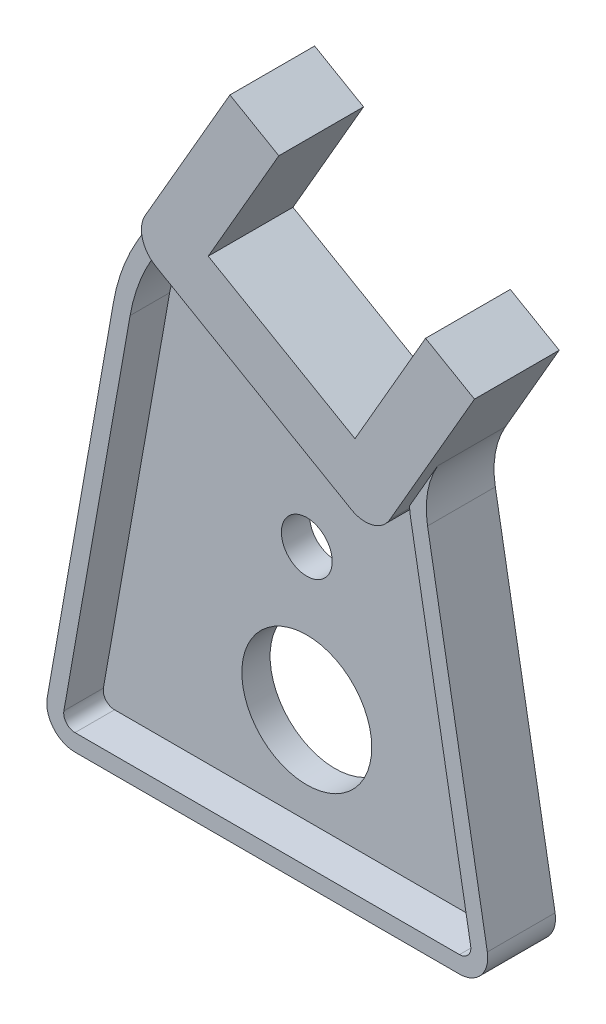
SolidWorks part; units mm, degrees
ref_plane "Front Plane" through (0, 0, 0) normal (0, 0, 1) x (1, 0, 0)
ref_plane "Top Plane" through (0, 0, 0) normal (0, 1, 0) x (1, 0, 0)
ref_plane "Right Plane" through (0, 0, 0) normal (1, 0, 0) x (0, 0, -1)
sketch "Sketch1" plane through (0, 0, 0) normal (0, 0, 1) x (1, 0, 0)
  line L0 (-34.0412, 0) -> (34.0412, 0)
  line L1 (0, 0) -> (0, 75) construction
  line L2 (-38.9653, 5.8682) -> (-27.243, 72.3487)
  line L3 (-18.6122, 91.5192) -> (-3.6122, 117.5)
  line L4 (-3.6122, 117.5) -> (5.0481, 112.5)
  line L5 (5.0481, 112.5) -> (-7.4519, 90.8494)
  line L6 (-7.4519, 90.8494) -> (18.5289, 75.8494)
  line L7 (18.5289, 75.8494) -> (31.0289, 97.5)
  line L8 (31.0289, 97.5) -> (39.6891, 92.5)
  line L9 (39.6891, 92.5) -> (30.1627, 75.9997)
  line L10 (17.859, 64.6891) -> (-16.782, 84.6891)
  line L11 (28.3809, 65.895) -> (38.9653, 5.8682)
  line L12 (5.5385, 83.3494) -> (18.0385, 105) construction
  line L13 (5.5385, 83.3494) -> (0, 75) construction
  line L14 (5.0481, 112.5) -> (31.0289, 97.5) construction
  line L15 (24.6891, 66.5192) -> (30.1627, 75.9997)
  line L16 (-23.0856, 83.771) -> (-18.6122, 91.5192)
  line L17 (25.4265, 65.3741) -> (36.0108, 5.3473)
  line L18 (-34.0412, 3) -> (34.0412, 3)
  line L19 (-36.0108, 5.3473) -> (-24.2885, 71.8278)
  line L20 (-20.4875, 82.271) -> (-18.3054, 86.0506)
  line L21 (-20.4875, 82.271) -> (-16.0141, 90.0192) construction
  circle A0 centre (0, 20) radius 11.5
  circle A1 centre (0, 45) radius 4.5
  arc A2 (34.0412, 0) -> (38.9653, 5.8682) centre (34.0412, 5) ccw
  arc A3 (-34.0412, 0) -> (-38.9653, 5.8682) centre (-34.0412, 5) cw
  arc A4 (-27.243, 72.3487) -> (-23.0856, 83.771) centre (7.2253, 66.271) cw
  arc A5 (28.3809, 65.895) -> (30.1627, 75.9997) centre (43.1531, 68.4997) cw
  arc A6 (24.6891, 66.5192) -> (17.859, 64.6891) centre (20.359, 69.0192) cw
  arc A7 (-16.782, 84.6891) -> (-18.6122, 91.5192) centre (-14.282, 89.0192) cw
  arc A8 (25.4265, 65.3741) -> (25.1877, 67.3829) centre (43.1531, 68.4997) cw
  arc A9 (34.0412, 3) -> (36.0108, 5.3473) centre (34.0412, 5) ccw
  arc A10 (-34.0412, 3) -> (-36.0108, 5.3473) centre (-34.0412, 5) cw
  arc A11 (-24.2885, 71.8278) -> (-20.4875, 82.271) centre (7.2253, 66.271) cw
  arc A12 (25.4265, 65.3741) -> (27.5646, 77.4997) centre (43.1531, 68.4997) cw construction
  point P4 (0, 0)
  point P20 (40, 0)
  point P25 (-40, 0)
  point P30 (18.0385, 105)
  dimension "D1" = 80
  dimension "D3" = 5
  dimension "D7" = 23
  dimension "D8" = 9
  dimension "D9" = 35
  dimension "D16" = 15
  dimension "D17" = 5
  dimension "D2" = 20
  dimension "D4" = 75
  dimension "D5" = 20
  dimension "D6" = 25
  dimension "D10" = 30
  dimension "D11" = 50
  dimension "D12" = 35
  dimension "D13" = 60
  dimension "D14" = 25
  dimension "D15" = 105
  dimension "D18" = 3
extrude "Boss-Extrude1" add sketch "Sketch1" along normal blind 5 contours A11 L19 A10 L18 A9 L17 A8 L15 A6 L10 A7 L20 A0 A1 | L19 A11 L20 A7 L16 A4 L2 A3 L0 A2 L11 A5 L15 A8 L17 A9 L18 A10 | A7 L10 A6 L15 L9 L8 L7 L6 L5 L4 L3 region at (-36.9499, 2.5594, 0) region at (26.9858, 72.0893, 0) region at (-1.1507, 38.1187, 0)
extrude "Boss-Extrude2" add sketch "Sketch1<3>" along normal blind 12 contours L19 A11 L20 A7 L16 A4 L2 A3 L0 A2 L11 A5 L15 A8 L17 A9 L18 A10 region at (-36.9499, 2.5594, 0)
sketch "Sketch1<3>" plane through (0, 0, 0) normal (0, 0, 1) x (1, 0, 0) same geometry as "Sketch1"
extrude "Boss-Extrude3" add sketch "Sketch1<4>" along normal blind 15 contours A7 L10 A6 L15 L9 L8 L7 L6 L5 L4 L3 region at (26.9858, 72.0893, 0)
sketch "Sketch1<4>" plane through (0, 0, 0) normal (0, 0, 1) x (1, 0, 0) same geometry as "Sketch1"
